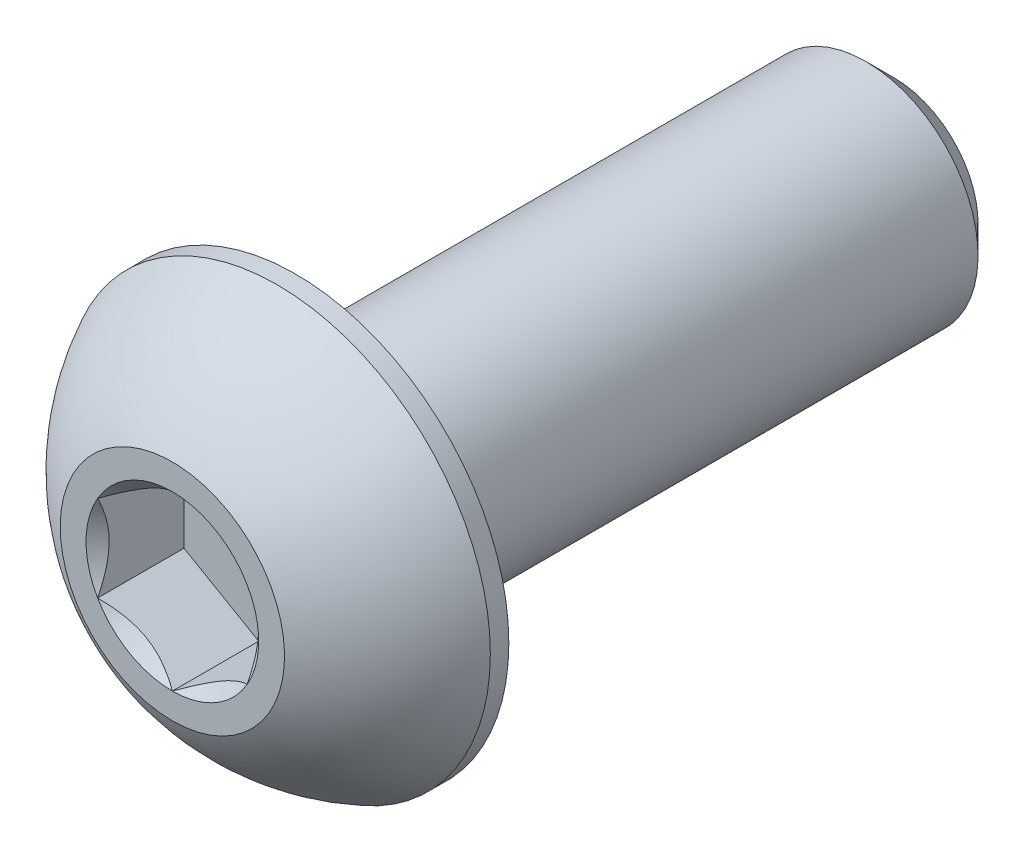
SolidWorks part; units mm, degrees
ref_plane "Front" through (0, 0, 0) normal (0, 0, 1) x (1, 0, 0)
ref_plane "Top" through (0, 0, 0) normal (0, 1, 0) x (1, 0, 0)
ref_plane "Right" through (0, 0, 0) normal (1, 0, 0) x (0, 0, -1)
sketch "Sketch1" plane through (0, 0, 0) normal (1, 0, 0) x (0, 0, -1)
  line L2 (1.65, 1.5) -> (9.65, 1.5)
  line L3 (9.65, 1.5) -> (9.65, 0)
  line L4 (9.65, 0) -> (1.65, 0)
  line L6 (1.4025, 2.85) -> (1.65, 2.85) construction
  line L7 (9.65, 1.5) -> (9.65, -1.5) construction
  line L8 (0, 0) -> (1.65, 0) construction
  line L9 (1.65, 2.85) -> (1.65, -2.85) construction
  line L11 (1.65, 1.5) -> (1.65, 0)
  line L13 (0, 1) -> (0, -1) construction
  line L14 (0, 1) -> (0, 1.5) construction
  arc A3 (0, 1.5) -> (1.4025, 2.85) centre (2.7948, 0) cw construction
  dimension "D1" = 0.2475
  dimension "Head Ht" = 1.65
  dimension "Head Dia" = 5.7
  dimension "Dia" = 3
  dimension "Lg" = 8
  dimension "Hex" = 2
revolve "Revolve1" add sketch "Sketch1" angle 360 mid plane about L4
sketch "Sketch3" plane through (0, 0, -9.65) normal (0, 0, -1) x (-1, 0, 0)
  circle A0 centre (0, 0) radius 1.5
curve "Helix/Spiral1" [suppressed] pitch 0.5 height 8.5 turns 17
sketch "Sketch2" plane through (0, 0, 0) normal (1, 0, 0) x (0, 0, -1)
  line L0 (9.65, 1.5) -> (10.0875, 1.5)
  line L1 (10.0875, 1.5) -> (9.9, 1.1752)
  line L2 (9.9, 1.1752) -> (9.8375, 1.1752)
  line L3 (9.8375, 1.1752) -> (9.65, 1.5)
  line L4 (9.7438, 1.3376) -> (9.9938, 1.3376) construction
  dimension "D1" = 60
  dimension "D2" = 0.0625
  dimension "D3" = 0.25
chamfer "Chamfer1" distance 0.375 angle 45 1 edges at (0, 1.5, -9.65)
sweep "Cut-Sweep1" [suppressed] cut profiles "Sketch2" path "Helix/Spiral1"
sketch "Sketch7" plane through (0, 0, 0) normal (1, 0, 0) x (0, 0, -1)
  line L6 (1.4025, 2.85) -> (1.65, 2.85) construction
  line L8 (0, 0) -> (1.65, 0) construction
  line L11 (1.65, 2.85) -> (1.65, -2.85) construction
  line L12 (1.4025, 2.85) -> (1.65, 2.85)
  line L13 (0, 0) -> (1.65, 0)
  line L14 (0, 1) -> (0, -1) construction
  line L15 (1.65, 2.85) -> (1.65, 0)
  line L16 (0, 1.5) -> (0, 0)
  arc A2 (1.4025, 2.85) -> (0, 1.5) centre (2.7948, 0) ccw construction
  arc A3 (1.4025, 2.85) -> (0, 1.5) centre (2.7948, 0) ccw
revolve "Revolve2" add sketch "Sketch7" angle 360 mid plane about L13
sketch "Sketch5" plane through (0, 0, 0) normal (0, 0, 1) x (1, 0, 0)
  line L1 (1, -0.5774) -> (1, 0.5774)
  line L2 (1, 0.5774) -> (0, 1.1547)
  line L3 (0, 1.1547) -> (-1, 0.5774)
  line L4 (-1, 0.5774) -> (-1, -0.5774)
  line L5 (-1, -0.5774) -> (0, -1.1547)
  line L6 (0, -1.1547) -> (1, -0.5774)
  circle A0 centre (0, 0) radius 1 construction
extrude "Cut-Extrude2" cut sketch "Sketch5" against normal blind 1.155
sketch "Sketch6" plane through (0, 0, 0) normal (0, 0, 1) x (1, 0, 0)
  circle A0 centre (0, 0) radius 1.1547
extrude "Cut-Extrude3" cut sketch "Sketch6" against normal blind 1.155 draft 45
sketch "Sketch9" [suppressed] plane through (0, 0, -6.6) normal (0, 0, 1) x (1, 0, 0)
  circle A2 centre (0, 0) radius 6
extrude "Boss-Extrude2" [suppressed] add sketch "Sketch9" against normal offset from surface (19 mm away) 32 up to face at (0, 1.125, -9.65)
sketch "Sketch10" plane through (0, 0, 0) normal (1, 0, 0) x (0, 0, -1)
  line L0 (9.65, 1.5) -> (9.65, -1.5) construction
  point P0 (8.9, -1.5)
  dimension "D1" = 0.75
equation "\"D3@Helix/Spiral1\" = \"Lg@Sketch1\" + \"D4@Helix/Spiral1\""
equation "\"D2@Sketch2\" = \"D4@Helix/Spiral1\" * .125"
equation "\"D3@Sketch2\" = \"D4@Helix/Spiral1\" * .5"
equation "\"D1@Chamfer1\" = \"D4@Helix/Spiral1\" * .75"
equation "\"D1@Cut-Extrude2\" = \"Head Ht@Sketch1\" * .7"
equation "\"D1@Sketch1\" = \"Head Ht@Sketch1\" * .15"
equation "\"D1@Sketch10\" = \"D4@Helix/Spiral1\" * 1.5"
equation "\"D1@Cut-Extrude3\" = \"D1@Cut-Extrude2\""
